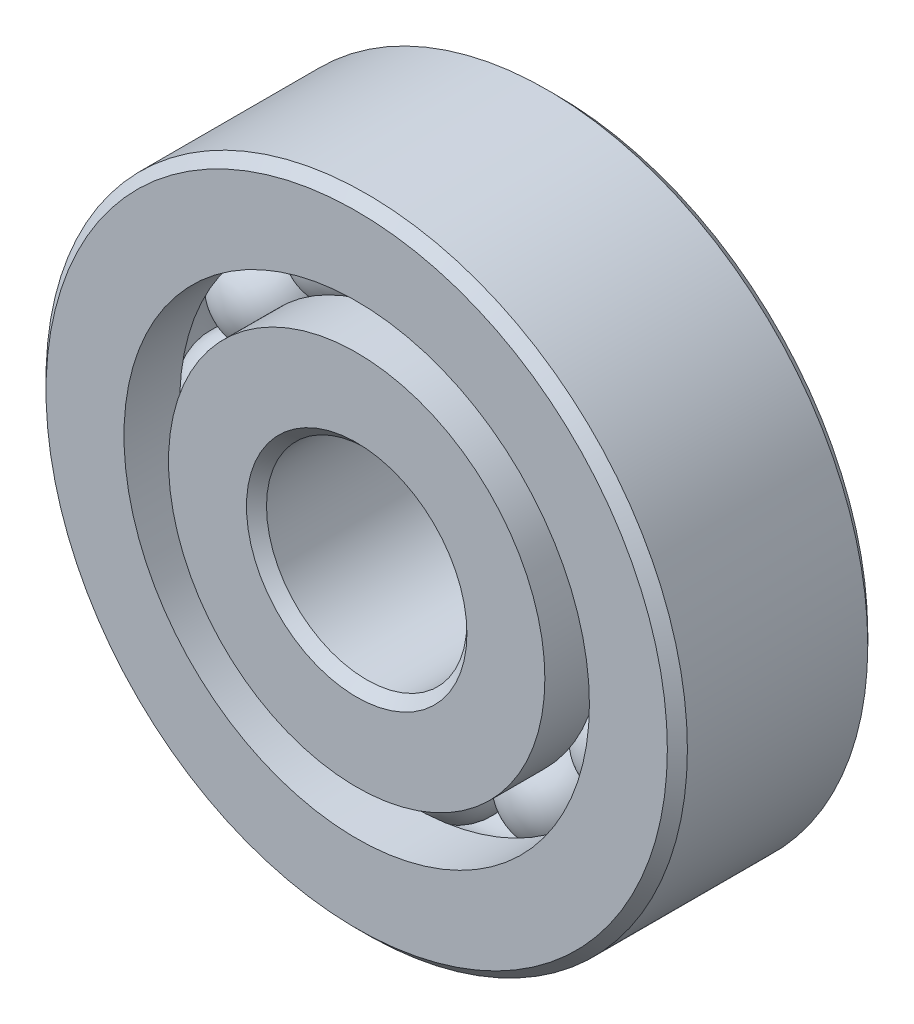
SolidWorks part; units mm, degrees
ref_plane "Front Plane" through (0, 0, 0) normal (0, 0, 1) x (1, 0, 0)
ref_plane "Top Plane" through (0, 0, 0) normal (0, 1, 0) x (1, 0, 0)
ref_plane "Right Plane" through (0, 0, 0) normal (1, 0, 0) x (0, 0, -1)
sketch "Sketch1" plane through (0, 0, 0) normal (1, 0, 0) x (0, 0, -1)
  line L0 (-2.5, 0) -> (2.5, 0) construction
  line L1 (0, 8) -> (0, -8) construction
  line L2 (2.25, 8) -> (-2.25, 8) construction
  line L3 (-2.25, 8) -> (-2.5, 7.75) construction
  line L4 (-2.5, 7.75) -> (-2.5, 5.8056) construction
  line L5 (-2.5, 5.8056) -> (-1.1111, 5.8056) construction
  line L6 (2.5, 5.8056) -> (1.1111, 5.8056) construction
  line L7 (2.5, 7.75) -> (2.5, 5.8056) construction
  line L8 (2.25, 8) -> (2.5, 7.75) construction
  line L9 (0, 8) -> (0, 5.25) construction
  line L10 (0, 5.25) -> (0, 2.5) construction
  arc A0 (-1.1111, 5.8056) -> (1.1111, 5.8056) centre (0, 5.25) cw construction
  arc A1 (-1.1111, 5.8056) -> (1.1111, 5.8056) centre (0, 5.25) ccw construction
  point P14 (0, 2.5)
  point P15 (0, -2.5)
  dimension "Width" = 5
  dimension "OD" = 16
  dimension "D1" = 45
  dimension "D2" = 0.25
  dimension "D3" = 2.2222
  dimension "Shaft Dia" = 5
  dimension "D4" = 0.5556
sketch "Sketch2" plane through (0, 0, 0) normal (1, 0, 0) x (0, 0, -1)
  line L0 (-2.5, 4.6944) -> (-1.1111, 4.6944)
  line L2 (-2.5, 4.6944) -> (-2.5, 2.75)
  line L3 (-2.5, 2.75) -> (-2.25, 2.5)
  line L4 (-2.25, 2.5) -> (2.25, 2.5)
  line L5 (0, 8) -> (0, -8) construction
  line L6 (0, 2.5) -> (0, 4.0077) construction
  line L7 (0, 4.0077) -> (0, 2.5) construction
  line L9 (-2.5, 7.75) -> (-2.5, 5.8056) construction
  line L10 (2.5, 4.6944) -> (1.1111, 4.6944)
  line L11 (2.5, 4.6944) -> (2.5, 2.75)
  line L12 (2.5, 2.75) -> (2.25, 2.5)
  line L13 (2.25, 8) -> (2.5, 7.75) construction
  line L14 (2.5, 7.75) -> (2.5, 5.8056) construction
  line L15 (2.5, 5.8056) -> (1.1111, 5.8056) construction
  line L16 (-2.5, 5.8056) -> (-1.1111, 5.8056) construction
  line L17 (2.25, 8) -> (-2.25, 8) construction
  line L18 (-2.25, 8) -> (-2.5, 7.75) construction
  line L19 (2.25, 8) -> (2.5, 7.75)
  line L20 (2.5, 7.75) -> (2.5, 5.8056)
  line L21 (2.5, 5.8056) -> (1.1111, 5.8056)
  line L22 (-2.5, 5.8056) -> (-1.1111, 5.8056)
  line L23 (-2.5, 7.75) -> (-2.5, 5.8056)
  line L24 (2.25, 8) -> (-2.25, 8)
  line L25 (-2.25, 8) -> (-2.5, 7.75)
  line L26 (-2.5, 2.75) -> (-2.25, 2.75) construction
  line L27 (-2.25, 2.75) -> (-2.25, 2.5) construction
  arc A0 (-1.1111, 4.6944) -> (1.1111, 4.6944) centre (0, 5.25) ccw
  arc A1 (1.1111, 5.8056) -> (-1.1111, 5.8056) centre (0, 5.25) ccw construction
  circle A2 centre (0, 5.25) radius 1.2423 construction
  arc A3 (-1.1111, 5.8056) -> (1.1111, 5.8056) centre (0, 5.25) cw
  dimension "D1" = 0.25
revolve "Revolve1" add sketch "Sketch2" angle 360 about L0
sketch "Sketch3" plane through (0, 0, 0) normal (1, 0, 0) x (0, 0, -1)
  line L0 (-1.2423, 5.25) -> (1.2423, 5.25)
  line L1 (0, 5.25) -> (0, 0) construction
  circle A1 centre (0, 5.25) radius 1.2423 construction
  arc A2 (-1.2423, 5.25) -> (1.2423, 5.25) centre (0, 5.25) cw
  arc A3 (1.1111, 5.8056) -> (-1.1111, 5.8056) centre (0, 5.25) ccw construction
  dimension "D1" = 2.4845
  dimension "D2" = 5.25
revolve "Revolve2" add sketch "Sketch3" angle 360 about L0
ref_axis "Axis1" through (0, 0, -2.5) along (0, 0, 1)
pattern_circular "CirPattern1" count 12 every 30 about axis through (0, 0, -2.5) along (0, 0, 1) of bodies 104
sketch "Sketch6" plane through (0, 0, 0) normal (0, 1, 0) x (1, 0, 0)
  point P0 (8, -2.5)
  point P1 (8, 2.5)
equation "\"D2@Sketch1\" = \"Width@Sketch1\"*.05"
equation "\"D3@Sketch1\" = \"Width@Sketch1\"/2.25"
equation "\"D4@Sketch1\" = \"D3@Sketch1\"/4"
equation "\"Balls@CirPattern1\"=\"D2@Sketch3\"*2*pi/\"D1@Sketch3\"-1"
equation "\"D2@CirPattern1\" = 360/\"Balls@CirPattern1\""
equation "\"D1@Sketch2\"=\"D2@Sketch1\""
equation "\"D1@Sketch6\"=\"Width@Sketch1\""
